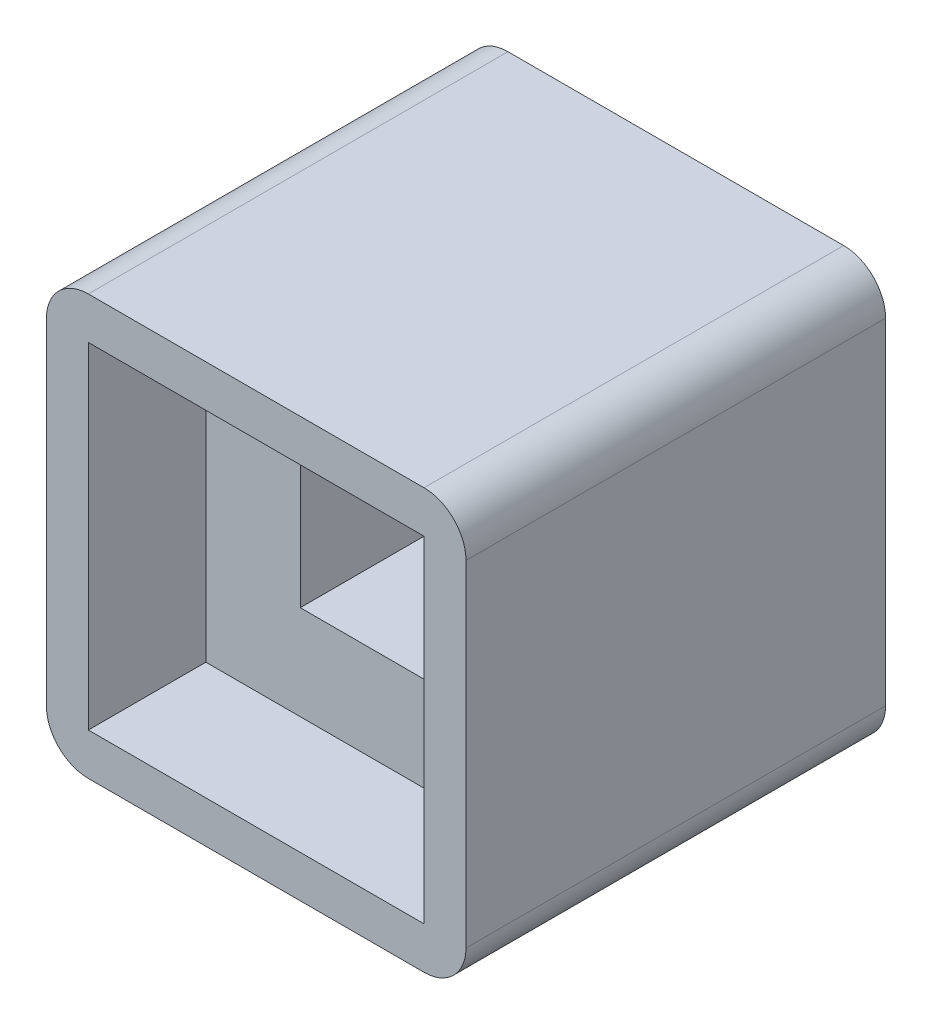
SolidWorks part; units mm, degrees
note: The reader was unsure of these and kept them because the rebuilt part matched: shared geometry of "草图6<3>".
ref_plane "前视基准面" through (0, 0, 0) normal (0, 0, 1) x (1, 0, 0)
ref_plane "上视基准面" through (0, 0, 0) normal (0, 1, 0) x (1, 0, 0)
ref_plane "右视基准面" through (0, 0, 0) normal (1, 0, 0) x (0, 0, -1)
sketch "草图1" plane through (0, 0, 0) normal (0, 1, 0) x (1, 0, 0)
  line L1 (0, 0) -> (100, 0)
  line L2 (0, 0) -> (0, 100)
  line L3 (0, 100) -> (100, 100)
  line L4 (100, 0) -> (100, 100)
extrude "凸台-拉伸1" add sketch "草图1" along normal blind 100
sketch "草图2" plane through (0, 0, -100) normal (0, 0, -1) x (-1, 0, 0)
  line L0 (22.9655, 50) -> (-122.9655, 50) construction
  line L1 (-50, -15.3083) -> (-50, 110.4447) construction
  circle A0 centre (-50, 50) radius 46
extrude "切除-拉伸1" cut sketch "草图2" against normal blind 15
fillet "圆角1" radius 10 4 edges at (100, 100, -50) (100, 0, -50) (0, 100, -50) (0, 0, -50)
sketch "草图3" plane through (0, 0, -85) normal (0, 0, -1) x (-1, 0, 0)
  line L0 (-50, 109.5011) -> (-50, -20.4661) construction
  line L1 (-61.8603, 26.8627) -> (-69.6151, 11.7345)
  line L2 (-38.1397, 26.8627) -> (-30.3849, 11.7345)
  arc A0 (-69.6151, 11.7345) -> (-30.3849, 11.7345) centre (-50, 50) ccw
  arc A1 (-61.8603, 26.8627) -> (-38.1397, 26.8627) centre (-50, 50) ccw
extrude "切除-拉伸2" cut sketch "草图3" against normal blind 8
ref_plane "基准面1" through (0, 0, -65) normal (0, 0, -1) x (-1, 0, 0)
sketch "草图6" plane through (0, 0, -65) normal (0, 0, -1) x (-1, 0, 0)
  line L0 (-69.6151, 11.7345) -> (-65.9658, 18.8537)
  line L2 (-30.3849, 11.7345) -> (-34.0342, 18.8537)
  arc A0 (-69.6151, 11.7345) -> (-30.3849, 11.7345) centre (-50, 50) ccw
  arc A1 (-65.9658, 18.8537) -> (-34.0342, 18.8537) centre (-50, 50) ccw
loft "切除-放样1" cut profiles "草图6" section face at (50, 17.3993, -77) section "草图6" connector at (61.8603, 26.8627, -77) connector at (65.9658, 18.8537, -65)
sketch "草图7" plane through (0, 0, 0) normal (0, -1, 0) x (1, 0, 0)
  line L0 (50, 7.1093) -> (50, -106.3534) construction
  line L1 (65.9658, -60.6462) -> (34.0342, -60.6462)
  line L2 (65.9658, -60.6462) -> (61.8603, -45.6462)
  line L7 (61.8603, -45.6462) -> (38.1397, -45.6462)
  line L8 (34.0342, -60.6462) -> (38.1397, -45.6462)
  point P5 (50, -60.6462)
  point P6 (50, -45.6462)
loft "切除-放样3" cut profiles "草图6<3>", "草图7" connector at (69.6151, 11.7345, -65) connector at (65.9658, 0, -60.6462)
sketch "草图6<3>" plane through (0, 0, -65) normal (0, 0, -1) x (-1, 0, 0) same geometry as "草图6"
sketch "草图8" plane through (0, 0, 0) normal (0, 0, 1) x (1, 0, 0)
  line L0 (100, 50) -> (0, 50) construction
  line L1 (100, 90) -> (100, 10) construction
  line L2 (0, 90) -> (0, 10) construction
  line L7 (50, 100) -> (50, 0) construction
  line L8 (10, 100) -> (90, 100) construction
  line L9 (10, 0) -> (90, 0) construction
  line L11 (10, 90) -> (90, 90)
  line L12 (10, 90) -> (10, 10)
  line L13 (10, 10) -> (90, 10)
  line L14 (90, 90) -> (90, 10)
  line L15 (10, 90) -> (90, 10) construction
  line L16 (10, 10) -> (90, 90) construction
  point P12 (50, 50)
extrude "切除-拉伸7" cut sketch "草图8" against normal blind 28
sketch "草图9" plane through (0, 0, -28) normal (0, 0, 1) x (1, 0, 0)
  line L0 (6.7561, 50) -> (94.8758, 50) construction
  line L1 (50, 90) -> (50, 10) construction
  line L2 (90, 90) -> (10, 90) construction
  line L3 (10, 10) -> (90, 10) construction
  line L5 (32.5, 67.5) -> (67.5, 67.5)
  line L6 (32.5, 67.5) -> (32.5, 32.5)
  line L7 (32.5, 32.5) -> (67.5, 32.5)
  line L8 (67.5, 67.5) -> (67.5, 32.5)
  line L9 (32.5, 67.5) -> (67.5, 32.5) construction
  line L10 (32.5, 32.5) -> (67.5, 67.5) construction
  point P8 (50, 50)
extrude "切除-拉伸8" cut sketch "草图9" against normal blind 33
sketch "草图10" plane through (0, 0, -85) normal (0, 0, -1) x (-1, 0, 0)
  line L0 (-50, 74.7582) -> (-50, 25.8246) construction
  line L2 (-70.6462, 50) -> (-27.5516, 50) construction
  circle A1 centre (-36.9185, 36.9185) radius 2.5
  circle A2 centre (-36.9185, 63.0815) radius 2.5
  circle A3 centre (-63.0815, 36.9185) radius 2.5
  circle A4 centre (-63.0815, 63.0815) radius 2.5
extrude "切除-拉伸9" cut sketch "草图10" against normal blind 4
sketch "草图11" plane through (0, 0, -81) normal (0, 0, -1) x (-1, 0, 0)
  circle A0 centre (-63.0815, 63.0815) radius 1
  circle A1 centre (-36.9185, 63.0815) radius 1
  circle A2 centre (-63.0815, 36.9185) radius 1
  circle A3 centre (-36.9185, 36.9185) radius 1
extrude "切除-拉伸10" cut sketch "草图11" against normal blind 20 and the other way through all
